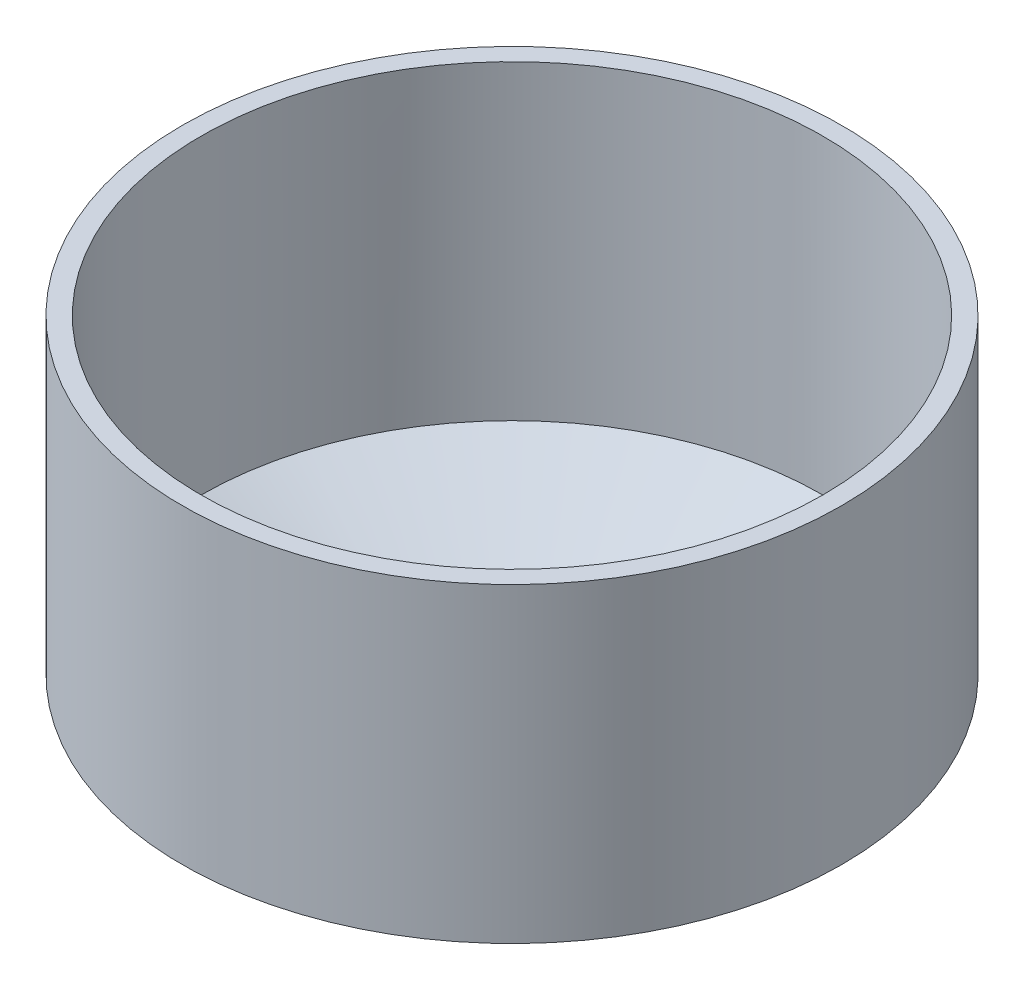
SolidWorks part; units mm, degrees
ref_plane "Front Plane" through (0, 0, 0) normal (0, 0, 1) x (1, 0, 0)
ref_plane "Top Plane" through (0, 0, 0) normal (0, 1, 0) x (1, 0, 0)
ref_plane "Right Plane" through (0, 0, 0) normal (1, 0, 0) x (0, 0, -1)
sketch "Sketch2" plane through (0, 0, 0) normal (0, 0, 1) x (1, 0, 0)
  line L0 (21.2, 20) -> (21.2, 0)
  line L1 (21.2, 0) -> (7.2, -6.9322)
  line L2 (7.2, -6.9322) -> (6, -6.9322)
  line L3 (6, -6.9322) -> (20, 0)
  line L4 (20, 0) -> (20, 20)
  line L5 (20, 20) -> (21.2, 20)
  line L6 (0, -1000) -> (0, 49000) construction
  dimension "D1" = 1.2
  dimension "D2" = 20
  dimension "D3" = 116.343
  dimension "D4" = 20
  dimension "D5" = 6
revolve "Revolve2" add sketch "Sketch2" angle 360 about L6
